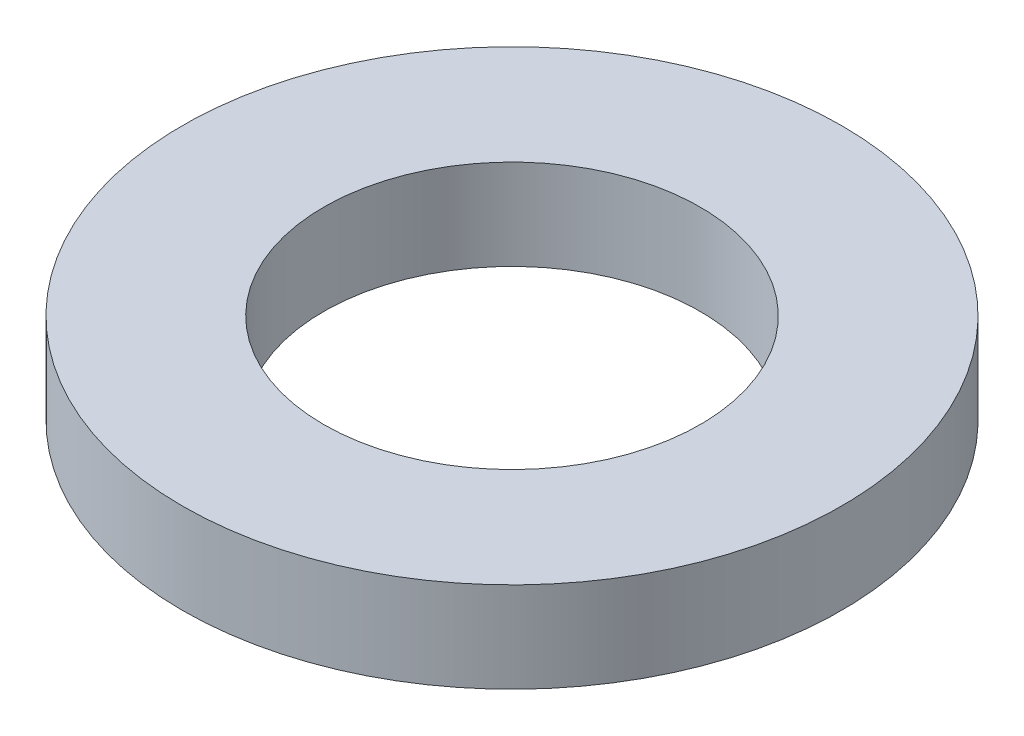
SolidWorks part; units mm, degrees
ref_plane "Front Plane" through (0, 0, 0) normal (0, 0, 1) x (1, 0, 0)
ref_plane "Top Plane" through (0, 0, 0) normal (0, 1, 0) x (1, 0, 0)
ref_plane "Right Plane" through (0, 0, 0) normal (1, 0, 0) x (0, 0, -1)
sketch "Sketch1" plane through (0, 0, 0) normal (0, 1, 0) x (1, 0, 0)
  circle A0 centre (0, 0) radius 87.5
  dimension "FLANGE_OD" = 175
extrude "Boss-Extrude1" add sketch "Sketch1" along normal blind 24
sketch "Sketch2" plane through (0, 0, 0) normal (0, 1, 0) x (1, 0, 0)
  circle A0 centre (0, 0) radius 50
  dimension "BORE_D" = 100
extrude "Cut-Extrude1" cut sketch "Sketch2" along normal through all
sketch "Sketch3" plane through (0, 24, 0) normal (0, 1, 0) x (1, 0, 0)
  circle A0 centre (0, 0) radius 34.0243 construction
  circle A1 centre (-34.0243, 0) radius 5.9519
  dimension "BOLT_D" = 11.9038
  dimension "BOLT_PCD" = 68.0487
extrude "Cut-Extrude2" cut sketch "Sketch3" against normal blind 20.9006 rebuild error yes
pattern_circular "CirPattern1" count 3 over 360 rebuild error yes
